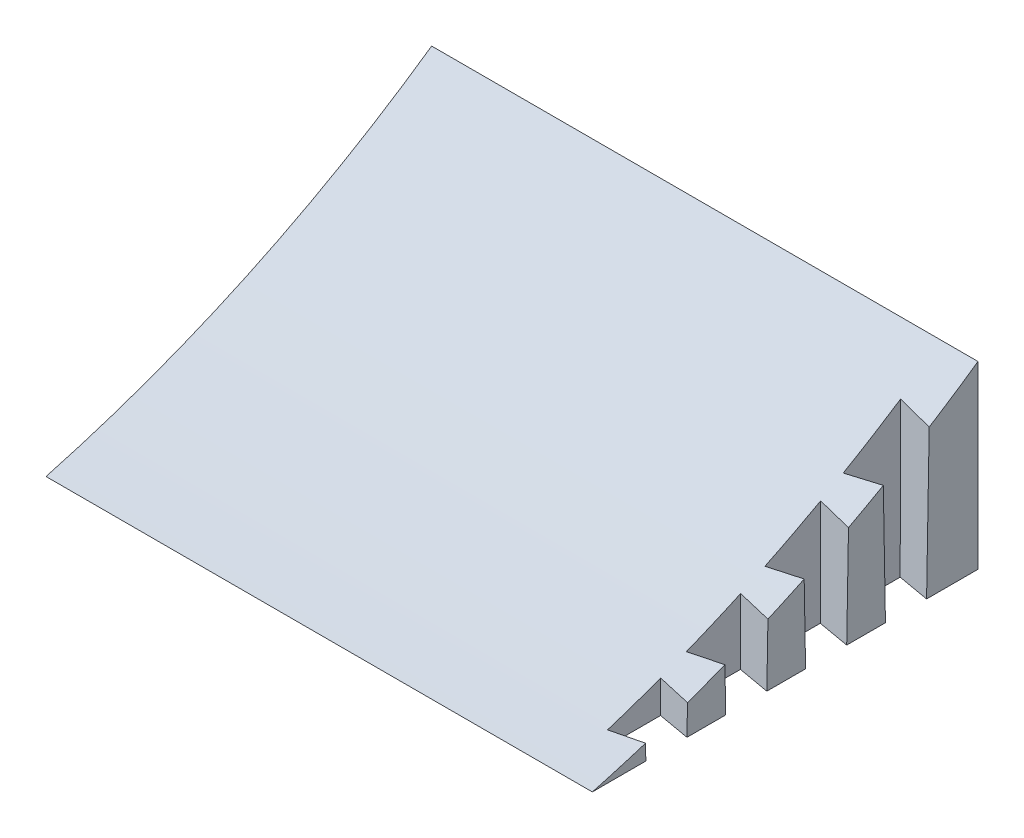
SolidWorks part; units mm, degrees
ref_plane "Front Plane" through (0, 0, 0) normal (0, 0, 1) x (1, 0, 0)
ref_plane "Top Plane" through (0, 0, 0) normal (0, 1, 0) x (1, 0, 0)
ref_plane "Right Plane" through (0, 0, 0) normal (1, 0, 0) x (0, 0, -1)
sketch "Sketch3" plane through (0, 0, 0) normal (1, 0, 0) x (0, 0, -1)
  line L0 (0, 0) -> (95.25, 0)
  line L1 (95.25, 0) -> (95.25, 44.45)
  arc A0 (0, 0) -> (95.25, 44.45) centre (-79.3399, 294.2927) ccw
  dimension "D3" = 304.8
  dimension "D1" = 44.45
  dimension "D2" = 95.25
extrude "Boss-Extrude1" add sketch "Sketch3" along normal blind 134.9375
sketch "Sketch4" plane through (0, 0, 0) normal (-1, 0, 0) x (0, 0, 1)
  line L0 (-95.25, 0) -> (-95.25, 44.45) construction
  line L5 (-95.25, 25.4) -> (-69.85, 25.4)
  line L12 (-95.25, 25.4) -> (-95.25, 6.35)
  line L13 (-95.25, 6.35) -> (-69.85, 6.35)
  line L14 (-69.85, 25.4) -> (-69.85, 6.35)
  line L15 (0, 0) -> (-95.25, 0) construction
  dimension "D1" = 25.4
  dimension "D2" = 19.05
  dimension "D3" = 6.35
extrude "Cut-Extrude1" cut sketch "Sketch4" against normal blind 6.35
sketch "Sketch5" plane through (6.35, 0, 0) normal (-1, 0, 0) x (0, 0, 1)
  line L0 (-69.85, 6.35) -> (-69.85, 25.4) construction
  line L3 (-95.25, 6.35) -> (-69.85, 6.35) construction
  circle A0 centre (-82.55, 15.875) radius 2.921
  dimension "D2" = 9.525
  dimension "D3" = 5.842
  dimension "D1" = 12.7
extrude "Cut-Extrude2" cut sketch "Sketch5" against normal blind 25.4
sketch "Sketch6" plane through (0, 0, 0) normal (0, -1, 0) x (1, 0, 0)
  line L0 (134.9375, -82.55) -> (127.0147, -83.947)
  line L1 (134.9375, 0) -> (134.9375, -95.25) construction
  line L2 (127.0147, -83.947) -> (127.0147, -70.993)
  line L3 (127.0147, -70.993) -> (134.9375, -72.39)
  line L4 (134.9375, -72.39) -> (134.9375, -82.55)
  line L5 (134.9375, -62.8227) -> (127.0147, -64.2197)
  line L6 (127.0147, -64.2197) -> (127.0147, -51.2657)
  line L7 (127.0147, -51.2657) -> (134.9375, -52.6627)
  line L8 (134.9375, -52.6627) -> (134.9375, -62.8227)
  line L9 (134.9375, -43.0953) -> (127.0147, -44.4923)
  line L10 (127.0147, -44.4923) -> (127.0147, -31.5383)
  line L11 (127.0147, -31.5383) -> (134.9375, -32.9353)
  line L12 (134.9375, -32.9353) -> (134.9375, -43.0953)
  line L13 (134.9375, -23.368) -> (127.0147, -24.765)
  line L14 (127.0147, -24.765) -> (127.0147, -11.811)
  line L15 (127.0147, -11.811) -> (134.9375, -13.208)
  line L16 (134.9375, -13.208) -> (134.9375, -23.368)
  line L18 (134.9375, -95.25) -> (0, -95.25) construction
  dimension "D1" = 80
  dimension "D2" = 80
  dimension "D4" = 12.7
  dimension "D5" = 12.954
  dimension "D6" = 10.16
  dimension "D7" = 13.208
  dimension "D3" = 4
extrude "Cut-Extrude3" cut sketch "Sketch6" against normal blind 38.1 draft 1 draft outward yes
